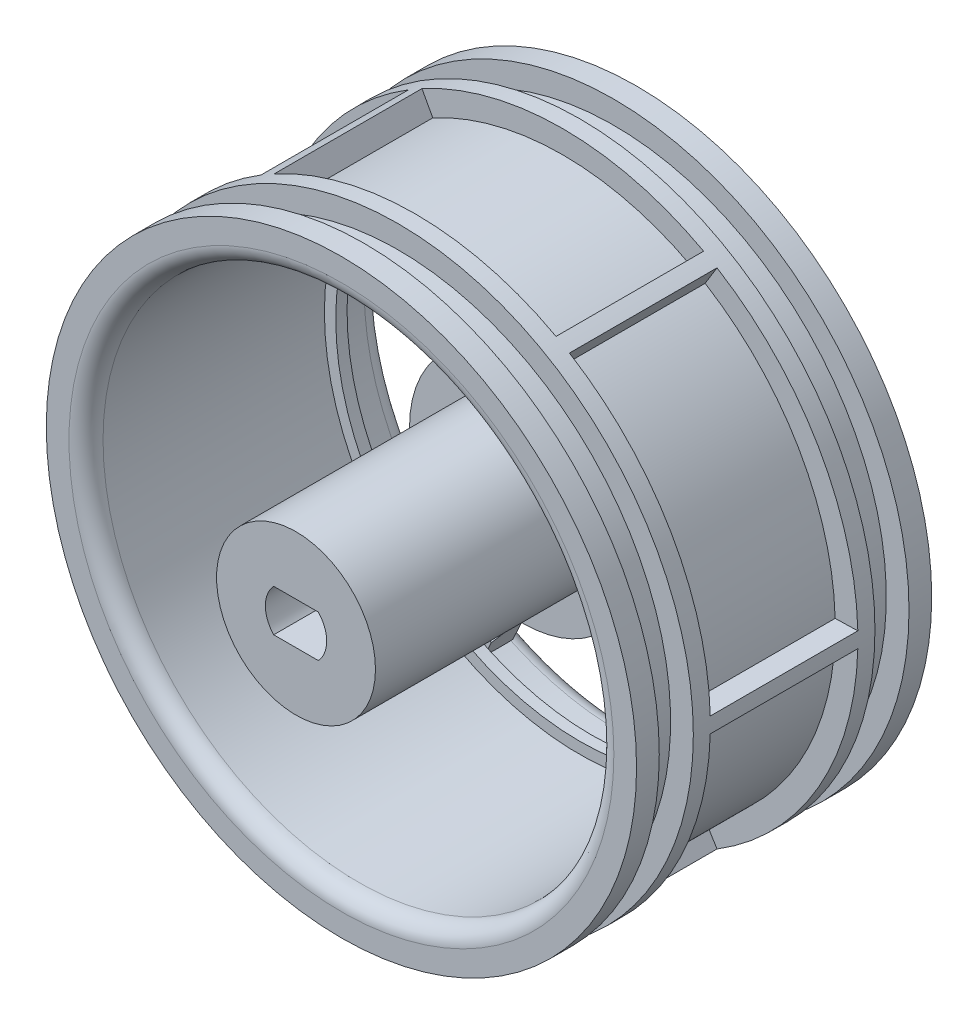
SolidWorks part; units mm, degrees
material "ABS"
ref_plane "Alzado" through (0, 0, 0) normal (0, 0, 1) x (1, 0, 0)
ref_plane "Planta" through (0, 0, 0) normal (0, 1, 0) x (1, 0, 0)
ref_plane "Vista lateral" through (0, 0, 0) normal (1, 0, 0) x (0, 0, -1)
ref_axis "Eje1" through (0, 0, -0.65) along (0, 0, 1)
sketch "Croquis1" plane through (0, 0, 0) normal (1, 0, 0) x (0, 0, -1)
  line L0 (-13, 22.5) -> (-13, 26)
  line L1 (-13, 26) -> (-11, 26)
  line L2 (-11, 26) -> (-11, 24)
  line L3 (-11, 24) -> (-8, 24)
  line L4 (-8, 24) -> (-8, 26)
  line L5 (-8, 26) -> (0, 26)
  line L6 (0, 26) -> (0, 22.5)
  line L7 (0, 22.5) -> (-13, 22.5)
  point P5 (0, 24.25)
  dimension "D1" = 26
  dimension "D2" = 13
  dimension "D3" = 3
  dimension "D4" = 2
  dimension "D5" = 2
  dimension "D6" = 1.5
revolve "Revolución1" add sketch "Croquis1" angle 360 about axis through (0, 0, -0.65) along (0, 0, 1)
mirror "Simetría1" about plane through (0, 0, 0) normal (0, 0, 1) of "Revolución1"
sketch "Croquis5" plane through (0, 0, 0) normal (1, 0, 0) x (0, 0, -1)
  line L0 (8, -26) -> (8, 26) construction
  line L3 (8, 22.5) -> (9, 22.5)
  line L4 (8, 22.5) -> (8, 21.5)
  line L5 (8, 21.5) -> (9, 21.5)
  line L6 (9, 22.5) -> (9, 21.5)
  dimension "D1" = 1
  dimension "D2" = 1
  dimension "D3" = 22.5
revolve "Revolución2" add sketch "Croquis5" angle 360 about axis through (0, 0, -0.65) along (0, 0, 1)
sketch "Croquis6" plane through (0, 0, 0) normal (1, 0, 0) x (0, 0, -1)
  line L0 (8, 26) -> (-8, 26) construction
  line L1 (-6.5, 26) -> (6.5, 26)
  line L2 (-6.5, 26) -> (-6.5, 24)
  line L3 (-6.5, 24) -> (6.5, 24)
  line L4 (6.5, 26) -> (6.5, 24)
  line L5 (-8, 26) -> (8, 26) construction
  point P10 (0, 26)
  point P11 (0, 26)
  dimension "D1" = 13
  dimension "D2" = 2
revolve "Cortar-Revolución1" cut sketch "Croquis6" angle 57 mid plane about axis through (0, 0, -0.65) along (0, 0, 1)
pattern_circular "MatrizC1" count 6 over 360 about axis through (0, 0, 0) along (0, 0, 1) of "Cortar-Revolución1"
sketch "Croquis8" plane through (0, 0, -13) normal (0, 0, -1) x (-1, 0, 0)
  line L0 (-4.422, 0) -> (4.422, 0)
  line L1 (4.422, 0) -> (3.5, 24)
  line L2 (3.5, 24) -> (-3.5, 24)
  line L3 (-3.5, 24) -> (-4.422, 0)
  point P3 (0, 24)
  point P8 (0, 0)
  dimension "D1" = 24
  dimension "D2" = 7
  dimension "D3" = 4.4
extrude "Saliente-Extruir1" add sketch "Croquis8" against normal blind 1.5
pattern_circular "MatrizC2" count 5 over 360 about axis through (0, 0, 0) along (0, 0, 1) of "Saliente-Extruir1"
fillet "Redondeo2" radius 5 5 edges at (-6.7956, -2.208, -12.25) (0, -7.1453, -12.25) (6.7956, -2.208, -12.25) (4.1999, 5.7807, -12.25) (-4.1999, 5.7807, -12.25)
sketch "Croquis9" plane through (0, 0, -11.5) normal (0, 0, 1) x (1, 0, 0)
  circle A0 centre (0, 0) radius 10
  dimension "D1" = 20
extrude "Saliente-Extruir2" add sketch "Croquis9" along normal blind 8.5
sketch "Croquis10" plane through (0, 0, -13) normal (0, 0, -1) x (-1, 0, 0)
  circle A0 centre (0, 0) radius 9
  dimension "D1" = 18
extrude "Cortar-Extruir1" cut sketch "Croquis10" against normal blind 4
sketch "Croquis11" plane through (0, 0, -3) normal (0, 0, 1) x (1, 0, 0)
  circle A0 centre (0, 0) radius 7
  dimension "D1" = 14
extrude "Saliente-Extruir3" add sketch "Croquis11" along normal blind 20
sketch "Croquis14" plane through (0, 0, 0) normal (1, 0, 0) x (0, 0, -1)
  line L0 (9, 22.3) -> (11.5, 22.3)
  line L1 (9, -22.5) -> (9, 22.5) construction
  line L2 (11.5, 22.5) -> (11.5, 22.2152) construction
  line L3 (11.5, 22.3) -> (11.5, 19.3)
  line L4 (11.5, 12.1299) -> (11.5, 22.2152) construction
  line L5 (9, 22.3) -> (9, 20.8)
  line L6 (9, -21.5) -> (9, 21.5) construction
  arc A0 (9, 20.8) -> (11.5, 19.3) centre (7.7893, 15.9488) cw
  dimension "D4" = 5
  dimension "D1" = 22.3
  dimension "D2" = 3
  dimension "D3" = 1.5
revolve "Revolución3" add sketch "Croquis14" angle 22 mid plane about axis through (0, 0, -0.65) along (0, 0, 1)
pattern_circular "MatrizC3" count 5 over 360 about axis through (0, 0, 0) along (0, 0, 1) of "Revolución3"
sketch "Croquis15" plane through (0, 0, -13) normal (0, 0, -1) x (-1, 0, 0)
  circle A0 centre (0, 0) radius 22.5
  circle A1 centre (0, 0) radius 22.3
  dimension "D1" = 45
  dimension "D2" = 0.2
extrude "Cortar-Extruir3" cut sketch "Croquis15" against normal up to next
fillet "Redondeo3" radius 1.5 2 edges at (-22.5, 0, 13) (-22.5, 0, -13)
fillet "Redondeo4" radius 2 25 edges at (3.9162, 21.9534, -11.5) (-3.9162, 21.9534, -11.5) (-19.6688, 10.5085, -11.5) (-22.0891, 3.0595, -11.5) (-16.0722, -15.4588, -11.5) (-9.7356, -20.0626, -11.5) (9.7356, -20.0626, -11.5) (16.0722, -15.4588, -11.5) (22.0891, 3.0595, -11.5) (19.6688, 10.5085, -11.5) (3.5764, 22.0113, -12.25) (-3.5764, 22.0113, -12.25) (0, 22.3, -13) (-19.8289, 10.2032, -12.25) (-22.0392, 3.4005, -12.25) (-21.2086, 6.8911, -13) (-15.8313, -15.7054, -12.25) (-10.0446, -19.9097, -12.25) (-13.1076, -18.0411, -13) (10.0446, -19.9097, -12.25) (15.8313, -15.7054, -12.25) (13.1076, -18.0411, -13) (22.0392, 3.4005, -12.25) (19.8289, 10.2032, -12.25) (21.2086, 6.8911, -13)
sketch "Croquis12" plane through (0, 0, 17) normal (0, 0, 1) x (1, 0, 0)
  line L0 (-1.9666, 1.85) -> (1.9666, 1.85)
  line L1 (-1.9666, -1.85) -> (1.9666, -1.85)
  arc A0 (-1.9666, 1.85) -> (-1.9666, -1.85) centre (0, 0) ccw
  arc A1 (1.9666, 1.85) -> (-1.9666, 1.85) centre (0, 0) ccw construction
  arc A2 (1.9666, -1.85) -> (1.9666, 1.85) centre (0, 0) ccw
  arc A3 (-1.9666, -1.85) -> (1.9666, -1.85) centre (0, 0) ccw construction
  dimension "D1" = 5.4
  dimension "D2" = 1.85
  dimension "D3" = 1.85
extrude "Cortar-Extruir2" cut sketch "Croquis12" against normal blind 20
sketch "Croquis16" plane through (0, 0, -9) normal (0, 0, -1) x (-1, 0, 0)
  circle A0 centre (0, 0) radius 5
  dimension "D1" = 10
extrude "Saliente-Extruir4" add sketch "Croquis16" along normal blind 2
fillet "Redondeo6" radius 0.5 1 edges at (-5, 0, -11)
sketch "Croquis17" plane through (0, 0, -9) normal (0, 0, -1) x (-1, 0, 0)
  circle A0 centre (-5, 5) radius 0.75
  dimension "D3" = 1.5
  dimension "D1" = 5
  dimension "D2" = 5
extrude "Saliente-Extruir5" add sketch "Croquis17" along normal blind 2.5 draft 4
pattern_circular "MatrizC4" count 4 over 360 about axis through (0, 0, 0) along (0, 0, 1) of "Saliente-Extruir5"
fillet "Redondeo7" radius 2 1 edges at (-9, 0, -9)
